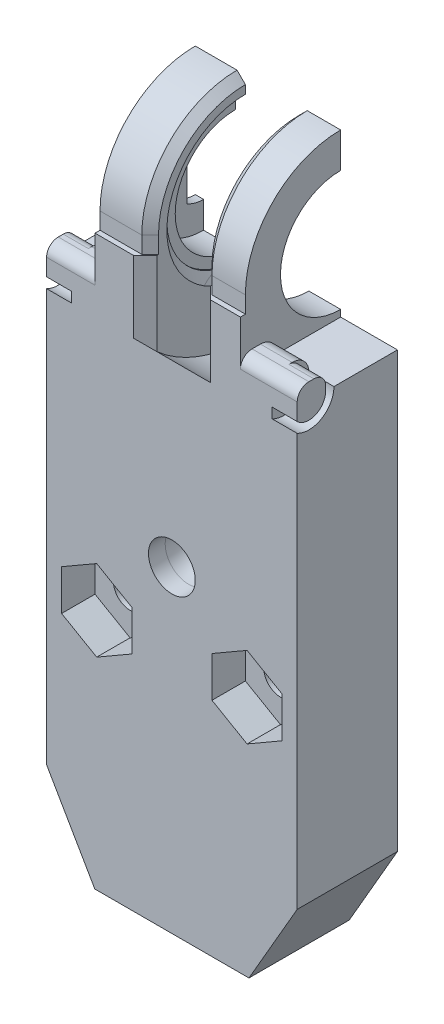
SolidWorks part; units mm, degrees
ref_plane "前视基准面" through (0, 0, 0) normal (0, 0, 1) x (1, 0, 0)
ref_plane "上视基准面" through (0, 0, 0) normal (0, 1, 0) x (1, 0, 0)
ref_plane "右视基准面" through (0, 0, 0) normal (1, 0, 0) x (0, 0, -1)
other "Configuration Table"
sketch "草图1" plane through (0, 0, 0) normal (0, 0, 1) x (1, 0, 0)
  line L1 (0, 0) -> (15, 0)
  line L2 (0, 0) -> (0, 23)
  line L3 (0, 23) -> (15, 23)
  line L4 (15, 0) -> (15, 23)
  dimension "D1" = 15
  dimension "D2" = 23
extrude "凸台-拉伸1" add sketch "草图1" along normal blind 12
ref_plane "基准面1" through (3.4, 0, 0) normal (-1, 0, 0) x (0, 0, 1)
sketch "草图2" plane through (3.4, 0, 0) normal (-1, 0, 0) x (0, 0, 1)
  line L0 (12, 23) -> (0, 23) construction
  line L1 (0.3, 23) -> (11.7, 23)
  line L2 (0.3, 23) -> (0.3, 27)
  line L4 (11.7, 23) -> (11.7, 27)
  line L5 (6, 0) -> (6, 23) construction
  line L6 (12, 0) -> (0, 0) construction
  arc A1 (11.7, 27) -> (0.3, 27) centre (6, 27) ccw
  circle A3 centre (6, 27) radius 3.6
  dimension "D2" = 4
  dimension "D3" = 7.2
  dimension "D1" = 11.4
extrude "凸台-拉伸2" add sketch "草图2" against normal blind 2.5
sketch "草图4" plane through (5.9, 0, 0) normal (1, 0, 0) x (0, 0, -1)
  circle A0 centre (-6, 27) radius 4.2
  circle M2 centre (-6, 27) radius 3.6
  line M6 (-11.7, 23) -> (-0.3, 23)
  dimension "D1" = 8.4
extrude "切除-拉伸1" cut sketch "草图4" against normal blind 0.6 and the other way blind 2.5 contours M2 | A0 M6 M2 | A0 M6
chamfer "倒角1" distance 0.5 angle 45 1 edges at (5.9, 31.2, 6)
ref_plane "基准面2" through (7.5, 0, 0) normal (-1, 0, 0) x (0, 0, 1)
mirror "镜向1" about plane through (7.5, 0, 0) normal (-1, 0, 0) of "切除-拉伸1", "倒角1", "凸台-拉伸2"
sketch "草图5" plane through (7.5, 0, 0) normal (-1, 0, 0) x (0, 0, 1)
  arc A2 (2.8, 31) -> (15.2, 31) centre (9, 31) ccw
  circle A3 centre (9, 31) radius 8.2
  dimension "D1" = 2
extrude "切除-拉伸2" cut sketch "草图5" against normal mid plane 3.2
sketch "草图6" plane through (3.4, 0, 0) normal (-1, 0, 0) x (0, 0, 1)
  line L3 (0.3, 27) -> (0.3, 23)
  line L4 (0.3, 23) -> (11.7, 23)
  line L7 (0.3, 23) -> (11.7, 23)
  line L9 (7, 28.7321) -> (7, 25.2679)
  line L15 (0.3, 27) -> (0.3, 23)
  line L17 (11.7, 23) -> (11.7, 27)
  line L18 (11.7, 23) -> (11.7, 27)
  circle A0 centre (6, 27) radius 3.6 construction
  arc A1 (11.7, 27) -> (0.3, 27) centre (6, 27) ccw
  arc A2 (11.7, 27) -> (0.3, 27) centre (6, 27) ccw
  circle A3 centre (6, 27) radius 3.6
  circle A6 centre (6, 27) radius 2
  point P11 (7, 27)
  circle M7 centre (6, 27) radius 3.6
  line M8 (0.3, 27) -> (0.3, 23)
  line M9 (0.3, 23) -> (11.7, 23)
  line M10 (11.7, 23) -> (11.7, 27)
  arc M11 (11.7, 27) -> (0.3, 27) centre (6, 27) ccw
  dimension "D3" = 4
  dimension "D2" = 1
  dimension "D1" = 0
extrude "凸台-拉伸3" add sketch "草图6" along normal blind 0.5 contours M11 M8 M9 M10 M7 | A6 M7 | L9 A6
sketch "草图7" plane through (0, 0, 0) normal (0, 0, -1) x (-1, 0, 0)
  line L0 (-15, 23) -> (0, 23) construction
  line L1 (-10.6, 23) -> (-4.4, 23)
  line L2 (-10.6, 23) -> (-10.6, 17.8)
  line L3 (-10.6, 17.8) -> (-4.4, 17.8)
  line L4 (-4.4, 23) -> (-4.4, 17.8)
  line L5 (-7.5, 0) -> (-7.5, 17.8) construction
  line L6 (0, 0) -> (-15, 0) construction
  dimension "D1" = 6.2
  dimension "D2" = 5.2
chamfer "倒角2" distance 4 angle 45 1 edges at (7.5, 23, 0)
ref_plane "基准面3" through (7.5, 0, 0) normal (-1, 0, 0) x (0, 0, 1)
sketch "草图15" plane through (7.5, 0, 0) normal (-1, 0, 0) x (0, 0, 1)
  line L0 (0.4645, 19.4645) -> (7.4645, 12.4645)
  line L1 (4, 23) -> (0, 19) construction
  line L2 (12, 11) -> (11, 11)
  line L3 (12, 0) -> (0, 0) construction
  line L4 (12, 23) -> (12, 0) construction
  line L5 (12, 23) -> (12, 0) construction
  arc A0 (11, 11) -> (7.4645, 12.4645) centre (11, 16) cw
  dimension "D2" = 11
  dimension "D1" = 5
  dimension "D3" = 1
sketch "草图40" plane through (0, 0, 12) normal (0, 0, 1) x (1, 0, 0)
  line L0 (5.9, 26) -> (5.9, 23)
  line L1 (15, 23) -> (0, 23) construction
  line L2 (5.9, 23) -> (5.9, 27) construction
  line L3 (5.9, 23) -> (0, 23)
  line L4 (0, 23) -> (2.9, 26)
  line L5 (2.9, 26) -> (5.9, 26)
  line L6 (2.9, 23) -> (2.9, 27) construction
  line L7 (5.9, 27) -> (2.9, 27) construction
  dimension "D1" = 1
extrude "凸台-拉伸4" add sketch "草图40" against normal up to surface (0.3 mm away) up to face at (4.4, 25, 11.7)
sketch "草图41" plane through (0, 0, 0) normal (-1, 0, 0) x (0, 0, 1)
  line L0 (11.7, 26) -> (7.85, 23)
  line L1 (11.7, 23) -> (4, 23) construction
  line L4 (11.7, 26) -> (11.7, 23)
  line L5 (11.7, 23) -> (12, 23)
  line L6 (12, 23) -> (12, 26)
  line L7 (12, 26) -> (11.7, 26)
  line L8 (11.7, 26) -> (11.7, 23)
  line L9 (11.7, 23) -> (12, 23)
  line L10 (12, 23) -> (12, 26)
  line L11 (12, 26) -> (11.7, 26)
  line M7 (12, 23) -> (11.7, 23)
  line M8 (11.7, 23) -> (4, 23)
  dimension "D1" = 0
extrude "凸台-拉伸5" add sketch "草图41" against normal blind 2.9 contours L8 L0 M8 | L10 L11 L8 M7
mirror "镜向3" about plane through (7.5, 0, 0) normal (-1, 0, 0) of "凸台-拉伸4", "凸台-拉伸5"
sketch "草图57" plane through (0, 0, 0) normal (0, 0, -1) x (-1, 0, 0)
  line L0 (-15, 6.5) -> (0, 6.5) construction
  line L1 (-15, 9.5) -> (0, 9.5) construction
  line L2 (-7.5, 17.8076) -> (-7.5, 0) construction
  line L5 (0, 19) -> (-15, 19)
  line L6 (-15, 19) -> (-15, 0)
  line L7 (-15, 0) -> (0, 0)
  line L8 (0, 0) -> (0, 19)
  line L10 (0, 19) -> (-15, 19)
  line L11 (-15, 19) -> (-15, 0)
  line L12 (-15, 0) -> (0, 0)
  line L13 (0, 0) -> (0, 19)
  circle A0 centre (-12, 6.5) radius 1.7
  circle A1 centre (-3, 6.5) radius 1.7
  dimension "D2" = 3
  dimension "D3" = 3.4
  dimension "D4" = 3
  dimension "D1" = 0
extrude "切除-拉伸3" cut sketch "草图57" against normal blind 2 contours A0 | A1
sketch "草图58" plane through (0, 0, 2) normal (0, 0, -1) x (-1, 0, 0)
  circle A0 centre (-12, 6.5) radius 1
  circle A1 centre (-3, 6.5) radius 1
  dimension "D1" = 2
extrude "切除-拉伸4" cut sketch "草图58" against normal up to next
sketch "草图59" plane through (0, 0, 12) normal (0, 0, 1) x (1, 0, 0)
  line L0 (15, 0) -> (15, 26) construction
  line L1 (3, 4.0751) -> (5.1, 5.2876)
  line L2 (5.1, 5.2876) -> (5.1, 7.7124)
  line L3 (5.1, 7.7124) -> (3, 8.9249)
  line L4 (3, 8.9249) -> (0.9, 7.7124)
  line L5 (0.9, 7.7124) -> (0.9, 5.2876)
  line L6 (0.9, 5.2876) -> (3, 4.0751)
  line L7 (12, 4.0751) -> (14.1, 5.2876)
  line L8 (14.1, 5.2876) -> (14.1, 7.7124)
  line L9 (14.1, 7.7124) -> (12, 8.9249)
  line L10 (12, 8.9249) -> (9.9, 7.7124)
  line L11 (9.9, 7.7124) -> (9.9, 5.2876)
  line L12 (9.9, 5.2876) -> (12, 4.0751)
  circle A0 centre (3, 6.5) radius 2.1 construction
  circle A1 centre (12, 6.5) radius 2.1 construction
  dimension "D1" = 4.2
extrude "切除-拉伸5" cut sketch "草图59" against normal blind 2 contours L2 L3 L4 L5 L6 L1 | L12 L7 L8 L9 L10 L11
sweep "切除-扫描1" cut path "草图15" circular profile diameter 2.8 parameters "D3"=2.8
sketch "草图79" plane through (7.5, 0, 0) normal (-1, 0, 0) x (0, 0, 1)
  arc A1 (-0.1177, 28.0068) -> (12.1941, 27.2693) centre (6, 27) ccw
  circle A2 centre (6, 27) radius 8
  dimension "D1" = 1.8
extrude "切除-拉伸7" cut sketch "草图79" against normal mid plane 3.2
sketch "草图78" plane through (0, 0, 0) normal (-1, 0, 0) x (0, 0, 1)
  line L0 (6, 0) -> (6, 33.9991)
  line L1 (12, 0) -> (0, 0)
  line L2 (12, 0) -> (12, 33.9991)
  line L3 (12, 33.9991) -> (0, 33.9991)
  line L4 (0, 0) -> (0, 33.9991)
  line M2 (7.85, 23) -> (4, 23)
  line M3 (4, 23) -> (0, 19)
  line M4 (0, 19) -> (0, 0)
  line M5 (0, 0) -> (12, 0)
extrude "切除-拉伸6" cut sketch "草图78" against normal through all contours L0 M5 M2 M3 M4 | L4 L0 L3 M3 M2
sketch "草图80" plane through (0, 23, 0) normal (0, 1, 0) x (1, 0, 0)
  line L1 (2.9, -7.85) -> (-1.8986, -7.85)
  line L2 (2.9, -7.85) -> (2.9, -12.9617)
  line L3 (2.9, -12.9617) -> (-1.8986, -12.9617)
  line L4 (-1.8986, -7.85) -> (-1.8986, -12.9617)
extrude "切除-拉伸8" cut sketch "草图80" along normal up to surface (3 mm away) up to face at (2.94, 26, 11.82)
sketch "草图81" plane through (0, 23, 0) normal (0, 1, 0) x (1, 0, 0)
  line L0 (11.6, -6) -> (11.6, -11.7) construction
  line L1 (15, -7.85) -> (11.6, -7.85)
  line L2 (15, -7.85) -> (15, -14.2486)
  line L3 (15, -14.2486) -> (11.6, -14.2486)
  line L4 (11.6, -7.85) -> (11.6, -14.2486)
extrude "切除-拉伸9" cut sketch "草图81" along normal up to surface (3 mm away)
sketch "草图82" plane through (15, 0, 0) normal (1, 0, 0) x (0, 0, -1)
  line L1 (-12, 23) -> (-6, 23) construction
  line L2 (-12, 0) -> (-12, 23) construction
  line L7 (-6, 23) -> (-12, 23)
  line L12 (-12, 23) -> (-12, 0)
  line L13 (-12, 0) -> (-6, 0)
  line L14 (-6, 0) -> (-6, 23)
  line L15 (-6, 23) -> (-12, 23)
  line L16 (-12, 23) -> (-12, 0)
  line L17 (-12, 0) -> (-6, 0)
  line L18 (-6, 0) -> (-6, 23)
  arc A0 (-10.3, 23) -> (-12, 22.2859) centre (-11.3, 23) cw
  circle A1 centre (-11.3, 23) radius 1.5
  dimension "D1" = 1
  dimension "D2" = 0.5
  dimension "D4" = 0.7
  dimension "D3" = 0
extrude "切除-拉伸10" cut sketch "草图82" against normal blind 1.5 contours L16 A1 L15 A0
mirror "镜向4" about plane through (7.5, 0, 0) normal (-1, 0, 0) of "切除-拉伸10"
chamfer "倒角3" distance 0.5 angle 45 4 edges at (5.9, 31.0305, 10.0305) (5.9, 26.5, 11.7) (9.1, 31.0305, 10.0305) (9.1, 26.5, 11.7)
chamfer "倒角4" distance 0.7 angle 45 2 edges at (5.9, 23.8542, 12) (9.1, 23.8542, 12)
sketch "草图83" plane through (0, 23, 0) normal (0, 1, 0) x (1, 0, 0)
  line L0 (0, -9.8) -> (1.5, -9.8) construction
  line L1 (1.5, -9.8) -> (1.5, -10.3) construction
  line L2 (1.5, -10.3) -> (0, -10.3) construction
  line L3 (0, -10.3) -> (0, -12) construction
  line L4 (0, -12) -> (2.9, -12) construction
  line L5 (2.9, -12) -> (2.9, -6) construction
  line L6 (2.9, -6) -> (0, -6) construction
  line L7 (0, -6) -> (0, -9.8) construction
  line L8 (15, -12) -> (15, -10.3) construction
  line L9 (15, -10.3) -> (13.5, -10.3) construction
  line L10 (13.5, -10.3) -> (13.5, -9.8) construction
  line L11 (13.5, -9.8) -> (15, -9.8) construction
  line L12 (15, -9.8) -> (15, -6) construction
  line L13 (15, -6) -> (11.6, -6) construction
  line L14 (11.6, -6) -> (11.6, -12) construction
  line L15 (11.6, -12) -> (15, -12) construction
  line L16 (0, -9.8) -> (1.5, -9.8)
  line L17 (1.5, -9.8) -> (1.5, -10.3)
  line L18 (1.5, -10.3) -> (0, -10.3)
  line L19 (0, -10.3) -> (0, -12)
  line L20 (0, -12) -> (2.9, -12)
  line L21 (2.9, -12) -> (2.9, -6)
  line L22 (2.9, -6) -> (0, -6)
  line L23 (0, -6) -> (0, -9.8)
  line L24 (15, -12) -> (15, -10.3)
  line L25 (15, -10.3) -> (13.5, -10.3)
  line L26 (13.5, -10.3) -> (13.5, -9.8)
  line L27 (13.5, -9.8) -> (15, -9.8)
  line L28 (15, -9.8) -> (15, -6)
  line L29 (15, -6) -> (11.6, -6)
  line L30 (11.6, -6) -> (11.6, -12)
  line L31 (11.6, -12) -> (15, -12)
  line L32 (1.5, -9.8) -> (2.9, -9.8)
  line L33 (13.5, -9.8) -> (11.6, -9.8)
  line M1 (15, -12) -> (15, -10.3)
  line M2 (15, -10.3) -> (13.5, -10.3)
  line M3 (13.5, -10.3) -> (13.5, -9.8)
  line M8 (11.6, -12) -> (15, -12)
extrude "凸台-拉伸6" add sketch "草图83" along normal blind 1 contours L33 L30 M3 M8 M1 M2 | L32 L17 L18 L19 L20 L21
fillet "圆角1" radius 0.7 4 edges at (13.3, 24, 12) (14.25, 24, 10.3) (0.75, 24, 10.3) (1.45, 24, 12)
fillet "圆角2" radius 1 2 edges at (12.55, 24, 9.8) (2.2, 24, 9.8)
chamfer "倒角5" distance 0.5 angle 45 2 edges at (5.9, 22.8503, 6.6481) (9.1, 22.8503, 6.6481)
sketch "草图86" plane through (0, 0, 0) normal (0, -1, 0) x (1, 0, 0)
  line L4 (0, 12) -> (0, 6)
  line L5 (0, 6) -> (15, 6)
  line L6 (15, 6) -> (15, 12)
  line L7 (15, 12) -> (0, 12)
  line L8 (0, 12) -> (0, 6)
  line L9 (0, 6) -> (15, 6)
  line L10 (15, 6) -> (15, 12)
  line L11 (15, 12) -> (0, 12)
  dimension "D1" = 0
extrude "凸台-拉伸7" add sketch "草图86" along normal blind 8
chamfer "倒角6" distance 5 angle 30 2 edges at (0, -8, 9) (15, -8, 9)
